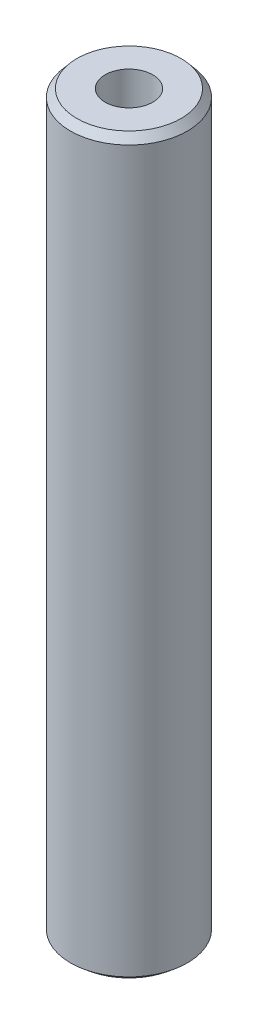
SolidWorks part; units mm, degrees
ref_plane "Front Plane" through (0, 0, 0) normal (0, 0, 1) x (1, 0, 0)
ref_plane "Top Plane" through (0, 0, 0) normal (0, 1, 0) x (1, 0, 0)
ref_plane "Right Plane" through (0, 0, 0) normal (1, 0, 0) x (0, 0, -1)
sketch "Sketch1" plane through (0, 0, 0) normal (0, 1, 0) x (1, 0, 0)
  circle A0 centre (0, 0) radius 45
  dimension "SHAFT_OD" = 90
extrude "Boss-Extrude1" add sketch "Sketch1" along normal blind 565.5403
sketch "Sketch2" plane through (0, 0, 0) normal (0, 1, 0) x (1, 0, 0)
  circle A0 centre (0, 0) radius 18.33
  dimension "BORE_D" = 36.6599
extrude "Cut-Extrude1" cut sketch "Sketch2" along normal through all
chamfer "Chamfer1" distance 5.9143 angle 39.776 2 edges at (0, 565.5403, 45) (0, 0, 45) first distance on face at (0, 565.5403, 45) first distance on face at (0, 0, 18.33)
